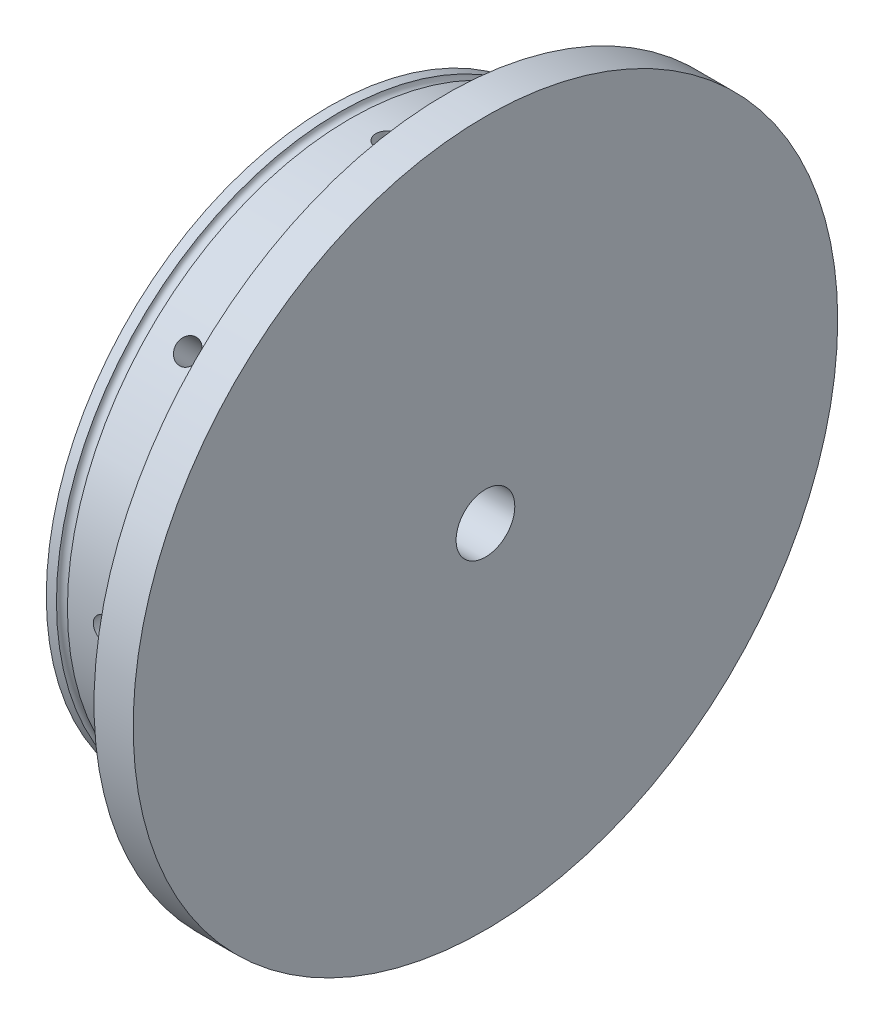
SolidWorks part; units mm, degrees
material "7075-T6 (SN)"
ref_plane "Front Plane" through (0, 0, 0) normal (0, 0, 1) x (1, 0, 0)
ref_plane "Top Plane" through (0, 0, 0) normal (0, 1, 0) x (1, 0, 0)
ref_plane "Right Plane" through (0, 0, 0) normal (1, 0, 0) x (0, 0, -1)
sketch "Sketch1" plane through (0, 0, 0) normal (1, 0, 0) x (0, 0, -1)
  circle A0 centre (0, 0) radius 57.15
  dimension "D1" = 114.3
extrude "Boss-Extrude1" add sketch "Sketch1" along normal blind 6.35
sketch "Sketch2" plane through (0, 0, 0) normal (-1, 0, 0) x (0, 0, 1)
  circle A0 centre (0, 0) radius 45.847
  dimension "D1" = 91.694
extrude "Boss-Extrude2" add sketch "Sketch2" along normal blind 19.05
sketch "Sketch3" plane through (-19.05, 0, 0) normal (-1, 0, 0) x (0, 0, 1)
  circle A0 centre (0, 0) radius 38.1762
  dimension "D1" = 76.3524
extrude "Cut-Extrude1" cut sketch "Sketch3" against normal blind 3.175
sketch "Sketch8" plane through (6.35, 0, 0) normal (1, 0, 0) x (0, 0, -1)
  circle A0 centre (0, 0) radius 4.7625
  dimension "D1" = 9.525
extrude "Cut-Extrude4" cut sketch "Sketch8" against normal through all
sketch "Sketch9" plane through (0, 0, 0) normal (0, 0, 1) x (1, 0, 0)
  line L0 (0, 0) -> (-19.05, 0)
  line L1 (0, 45.847) -> (0, -45.847) construction
  line L2 (-19.05, 45.847) -> (-19.05, -45.847) construction
  line L3 (0, 0) -> (-19.05, -14.986)
  line L5 (-19.05, 0) -> (-19.05, -14.986)
  dimension "D1" = 14.986
revolve "Cut-Revolve2" cut sketch "Sketch9" angle 360 about L0
sketch "Sketch5" plane through (0, 0, 0) normal (0, 0, 1) x (1, 0, 0)
  line L0 (0, 45.847) -> (-19.05, 45.847) construction
  line L1 (-19.05, 45.847) -> (-19.05, -45.847) construction
  line L2 (0, 0) -> (-28.6633, 0) construction
  circle A0 centre (-16.51, 45.847) radius 0.889
  dimension "D1" = 1.778
  dimension "D2" = 2.54
revolve "Cut-Revolve1" cut sketch "Sketch5" angle 360 about L2
ref_plane "Plane1" through (0, 0, 45.847) normal (0, 0, 1) x (1, 0, 0)
sketch "Sketch6" plane through (0, 0, 45.847) normal (0, 0, 1) x (1, 0, 0)
  line L0 (0, 45.847) -> (0, -45.847) construction
  circle A0 centre (-9.525, 0) radius 1.905
  dimension "D1" = 3.81
  dimension "D2" = 9.525
extrude "Cut-Extrude3" cut sketch "Sketch6" against normal blind 6.35
pattern_circular "CirPattern1" count 8 every 45 about axis through (-19.05, 0, 0) along (1, 0, 0) of "Cut-Extrude3"
sketch "Sketch10" plane through (-15.875, 0, 0) normal (-1, 0, 0) x (0, 0, 1)
  circle A0 centre (0, 33.3375) radius 1.1303
  circle A1 centre (23.5732, 23.5732) radius 1.1303
  circle A2 centre (33.3375, 0) radius 1.1303
  circle A3 centre (23.5732, -23.5732) radius 1.1303
  circle A4 centre (0, -33.3375) radius 1.1303
  circle A5 centre (-23.5732, -23.5732) radius 1.1303
  circle A6 centre (-33.3375, 0) radius 1.1303
  circle A7 centre (-23.5732, 23.5732) radius 1.1303
  point P19 (0, 0)
  dimension "D2" = 2.2606
  dimension "D1" = 33.3375
  dimension "D3" = 8
extrude "Cut-Extrude5" cut sketch "Sketch10" against normal blind 5.08
